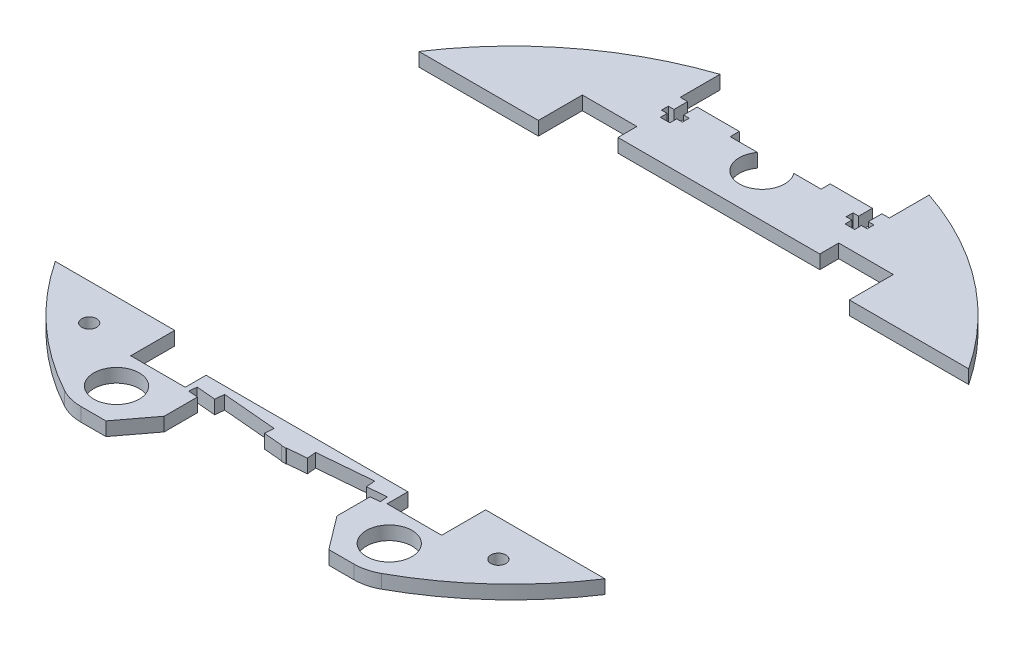
SolidWorks part; units mm, degrees
ref_plane "Front Plane" through (0, 0, 0) normal (0, 0, 1) x (1, 0, 0)
ref_plane "Top Plane" through (0, 0, 0) normal (0, 1, 0) x (1, 0, 0)
ref_plane "Right Plane" through (0, 0, 0) normal (1, 0, 0) x (0, 0, -1)
sketch "Sketch1" plane through (0, 0, 0) normal (0, 1, 0) x (1, 0, 0)
  line L0 (-30.03, -64.8129) -> (30.03, -64.8129)
  line L1 (0, -85) -> (0, 0) construction
  line L2 (0, -85) -> (32.4891, -64.8129) construction
  arc A0 (34.8348, -63.5829) -> (-34.8348, -63.5829) centre (0, 0) ccw
  circle A1 centre (0, -85) radius 38.25 construction
  arc A2 (30.03, -64.8129) -> (34.8348, -63.5829) centre (30.03, -54.8129) ccw
  arc A3 (-30.03, -64.8129) -> (-34.8348, -63.5829) centre (-30.03, -54.8129) cw
  dimension "D1" = 145
  dimension "D2" = 76.5
  dimension "D4" = 10
  dimension "D3" = 85
extrude "Boss-Extrude1" add sketch "Sketch1" along normal blind 3
sketch "Sketch2" plane through (0, 3, 0) normal (0, 1, 0) x (1, 0, 0)
  line L5 (22.2, -49.6757) -> (22.2, -45.1)
  line L6 (22.2, -45.1) -> (-22.2, -45.1)
  line L7 (-22.2, -45.1) -> (-22.2, -49.6757)
  line L8 (22.2, 49.6757) -> (22.2, 45.5)
  line L9 (-34.2, -49.6757) -> (-22.2, -49.6757) construction
  line L10 (-34.2, -49.6757) -> (-34.2, 49.6757) construction
  line L11 (-34.2, 49.6757) -> (-22.2, 49.6757) construction
  line L19 (34.2, 49.6757) -> (22.2, 49.6757) construction
  line L20 (34.2, -49.6757) -> (34.2, 49.6757) construction
  line L21 (34.2, -49.6757) -> (22.2, -49.6757) construction
  line L22 (22.2, 45.5) -> (-22.2, 45.5)
  line L23 (-22.2, 45.5) -> (-22.2, 49.6757)
  line L35 (-34.2, -49.6757) -> (-22.2, -49.6757)
  line L36 (-34.2, -49.6757) -> (-34.2, 49.6757)
  line L37 (-34.2, 49.6757) -> (-22.2, 49.6757)
  line L55 (34.2, 49.6757) -> (22.2, 49.6757)
  line L56 (34.2, -49.6757) -> (34.2, 49.6757)
  line L57 (34.2, -49.6757) -> (22.2, -49.6757)
  dimension "D1" = 45.1
  dimension "D2" = 45.5
extrude "Cut-Extrude1" cut sketch "Sketch2" against normal through all contours L55 L37 L36 L35 L7 L6 L5 L57 L56 region at (0, 3, -0.1256)
sketch "Sketch3" plane through (0, 3, 0) normal (0, 1, 0) x (1, 0, 0)
  line L0 (-34.2, 40) -> (-34.2, -40)
  line L1 (-72.5, -40) -> (-34.2, -40)
  line L2 (-72.5, -40) -> (-72.5, 40)
  line L3 (-72.5, 40) -> (-34.2, 40)
  line L4 (72.5, -40) -> (72.5, 40)
  line L5 (-72.5, -40) -> (72.5, 40) construction
  line L6 (-72.5, 40) -> (72.5, -40) construction
  line L7 (-34.2, -49.6757) -> (-34.2, 49.6757) construction
  line L8 (34.2, 40) -> (34.2, -40)
  line L9 (34.2, -49.6757) -> (34.2, 49.6757) construction
  line L10 (34.2, 40) -> (72.5, 40)
  line L11 (34.2, -40) -> (72.5, -40)
  arc A0 (34.8348, -63.5829) -> (-34.8348, -63.5829) centre (0, 0) ccw construction
  point P0 (0, 0)
  dimension "D1" = 80
extrude "Cut-Extrude2" cut sketch "Sketch3" against normal through all
sketch "Sketch4" plane through (0, 3, 0) normal (0, 1, 0) x (1, 0, 0)
  line L0 (-21.0702, -50.0262) -> (-0.6482, -51.8129)
  line L1 (21.0702, -50.0262) -> (20.922, -48.3326)
  line L2 (0.6482, -51.8129) -> (0.5, -50.1193)
  line L3 (20.922, -48.3326) -> (0.5, -50.1193)
  line L4 (0, 0) -> (0, -64.8129) construction
  line L5 (-30.03, -64.8129) -> (30.03, -64.8129) construction
  line L6 (-20.922, -48.3326) -> (-0.5, -50.1193)
  line L7 (-0.6482, -51.8129) -> (-0.5, -50.1193)
  line L8 (-21.0702, -50.0262) -> (-20.922, -48.3326)
  line L14 (21.0702, -50.0262) -> (0.6482, -51.8129)
  dimension "D1" = 1.7
  dimension "D2" = 20.5
  dimension "D3" = 5
  dimension "D4" = 13
  dimension "D5" = 0.5
extrude "Cut-Extrude3" cut sketch "Sketch4" against normal through all
sketch "Sketch5" plane through (0, 3, 0) normal (0, 1, 0) x (1, 0, 0)
  line L0 (-19, -64.8129) -> (-19, -50.2073)
  line L4 (0.6482, -51.8129) -> (21.0702, -50.0262) construction
  line L5 (16.6882, -48.7031) -> (4.7338, -49.7489)
  line L6 (16.6882, -48.7031) -> (16.5139, -46.7107)
  line L7 (4.7338, -49.7489) -> (4.5595, -47.7565)
  line L8 (16.5139, -46.7107) -> (4.5595, -47.7565)
  line L9 (20.922, -48.3326) -> (0.5, -50.1193) construction
  line L10 (0, 0) -> (0, -50.2073) construction
  line L11 (19, -64.8129) -> (19, -50.2073)
  line L13 (-16.5139, -46.7107) -> (-4.5595, -47.7565)
  line L14 (-4.7338, -49.7489) -> (-4.5595, -47.7565)
  line L15 (-16.6882, -48.7031) -> (-16.5139, -46.7107)
  line L16 (-16.6882, -48.7031) -> (-4.7338, -49.7489)
  line L22 (-30.03, -64.8129) -> (30.03, -64.8129) construction
  line L23 (19, -50.2073) -> (-19, -50.2073)
  line L25 (-19, -64.8129) -> (19, -64.8129)
  point P14 (10.711, -49.226)
  point P15 (10.711, -49.226)
  dimension "D1" = 12
  dimension "D2" = 38
  dimension "D4" = 2
extrude "Cut-Extrude4" cut sketch "Sketch5" against normal through all
sketch "Sketch6" plane through (0, 3, 0) normal (0, 1, 0) x (1, 0, 0)
  line L0 (0, 0) -> (0, 60) construction
  line L1 (-23, 72.5) -> (23, 72.5)
  line L2 (-23, 72.5) -> (-23, 60)
  line L3 (-23, 60) -> (-10, 60)
  line L4 (23, 72.5) -> (23, 60)
  line L5 (10, 60) -> (23, 60)
  line L7 (10, 60) -> (10, 58)
  line L8 (10, 58) -> (-10, 58)
  line L9 (-10, 60) -> (-10, 58)
  arc A1 (60.4669, 40) -> (-60.4669, 40) centre (0, 0) ccw construction
  point P14 (0, 58)
  dimension "D1" = 20
  dimension "D2" = 46
  dimension "D3" = 60
  dimension "D4" = 2
extrude "Cut-Extrude5" cut sketch "Sketch6" against normal through all
sketch "Sketch7" plane through (0, 3, 0) normal (0, 1, 0) x (1, 0, 0)
  line L0 (0, 0) -> (0, -31.2827) construction
  circle A0 centre (-30, -57) radius 5
  circle A4 centre (30, -57) radius 5
  dimension "D1" = 10
  dimension "D2" = 30
  dimension "D3" = 57
extrude "Cut-Extrude6" cut sketch "Sketch7" against normal through all
sketch "Sketch9" plane through (0, 3, 0) normal (0, 1, 0) x (1, 0, 0)
  line L0 (-23, 60) -> (-10, 60) construction
  line L1 (22.62, 57) -> (18.02, 57)
  line L2 (22.62, 57) -> (22.62, 55.5)
  line L3 (22.62, 55.5) -> (18.02, 55.5)
  line L4 (18.02, 57) -> (18.02, 55.5)
  line L5 (0, 0) -> (0, 44) construction
  line L7 (-18.02, 57) -> (-18.02, 55.5)
  line L8 (-22.62, 55.5) -> (-18.02, 55.5)
  line L9 (-22.62, 57) -> (-22.62, 55.5)
  line L10 (-22.62, 57) -> (-18.02, 57)
  point P4 (20.32, 55.5)
  dimension "D1" = 20.32
  dimension "D2" = 1.5
  dimension "D3" = 4.6
  dimension "D4" = 3
extrude "Cut-Extrude8" cut sketch "Sketch9" against normal through all
sketch "Sketch10" plane through (0, 3, 0) normal (0, 1, 0) x (1, 0, 0)
  line L0 (22.62, 57) -> (18.02, 57) construction
  line L1 (21.37, 57) -> (19.27, 57)
  line L2 (21.37, 57) -> (21.37, 60)
  line L3 (21.37, 60) -> (19.27, 60)
  line L4 (19.27, 57) -> (19.27, 60)
  line L5 (-23, 60) -> (-10, 60) construction
  line L6 (0, 0) -> (0, 44) construction
  line L8 (18.02, 55.5) -> (22.62, 55.5) construction
  line L9 (21.37, 55.5) -> (19.27, 55.5)
  line L10 (21.37, 55.5) -> (21.37, 54)
  line L11 (21.37, 54) -> (19.27, 54)
  line L12 (19.27, 55.5) -> (19.27, 54)
  line L13 (-19.27, 55.5) -> (-19.27, 54)
  line L14 (-21.37, 54) -> (-19.27, 54)
  line L15 (-21.37, 55.5) -> (-21.37, 54)
  line L16 (-21.37, 55.5) -> (-19.27, 55.5)
  line L17 (-19.27, 57) -> (-19.27, 60)
  line L18 (-21.37, 60) -> (-19.27, 60)
  line L19 (-21.37, 57) -> (-21.37, 60)
  line L20 (-21.37, 57) -> (-19.27, 57)
  point P14 (20.32, 57)
  point P16 (20.32, 57)
  dimension "D1" = 2.1
  dimension "D2" = 6
extrude "Cut-Extrude9" cut sketch "Sketch10" against normal through all
sketch "Sketch11" plane through (0, 3, 0) normal (0, 1, 0) x (1, 0, 0)
  line L0 (0, 0) -> (0, 55) construction
  circle A0 centre (0, 55) radius 5
  dimension "D2" = 10
  dimension "D1" = 55
extrude "Cut-Extrude10" cut sketch "Sketch11" against normal through all
sketch "Sketch13" plane through (0, 3, 0) normal (0, 1, 0) x (1, 0, 0)
  line L0 (19, -57.5101) -> (24.515, -64.8129)
  line L1 (19, -64.8129) -> (19, -50.2073) construction
  line L2 (19, -64.8129) -> (30.03, -64.8129) construction
  line L3 (24.515, -64.8129) -> (19, -64.8129)
  line L4 (19, -64.8129) -> (19, -57.5101)
  line L5 (0, 0) -> (0, -25.0729) construction
  line L6 (-19, -64.8129) -> (-19, -57.5101)
  line L7 (-24.515, -64.8129) -> (-19, -64.8129)
  line L8 (-19, -57.5101) -> (-24.515, -64.8129)
extrude "Cut-Extrude11" cut sketch "Sketch13" against normal through all
sketch "Sketch14" plane through (0, 3, 0) normal (0, 1, 0) x (1, 0, 0)
  line L1 (0, 0) -> (0, -20.685) construction
  circle A0 centre (45, -48) radius 1.65
  circle A1 centre (-45, -48) radius 1.65
  dimension "D3" = 3.3
  dimension "D1" = 45
  dimension "D2" = 48
extrude "Cut-Extrude12" cut sketch "Sketch14" against normal through all
equation "\"smallPulleyTeeth\"= 30"
equation "\"largePulleyTeeth\"= 30"
equation "\"eighthThick\"= 3.0mm"
equation "\"sixteenthThick\" = 1.7mm"
equation "\"quarterThick\"=6.0mm"
equation "\"OD\" = 145mm"
equation "\"puckAngle\" = 60.5deg"
equation "\"puckDiam\" = 76.5mm"
equation "\"axlePress\" = 5.9mm"
equation "\"press\" = 0.2mm"
equation "\"wheelClear\" = 0.3mm"
equation "\"10-32clear\" = 4.8mm"
equation "\"6-32clear\" = 3.3mm"
equation "\"8-32clear\" = 4.0mm"
equation "\"4-40clear\" = 3.0mm"
equation "\"wheelHeight\" = 22mm"
equation "\"wheelWell\" = 65mm"
equation "\"D1@Sketch1\"=\"OD\""
equation "\"D1@Boss-Extrude1\"=\"eighthThick\""
equation "\"D2@Sketch1\"=\"puckDiam\""
equation "\"puckDist\" = 85mm"
equation "\"scoopFillet\" = 5mm"
equation "\"10-32tap\" = 4.45mm"
equation "\"ledSmall\" = 3.1mm"
equation "\"ledLarge\" = 4.2mm"
equation "\"ledLength\" = 4.2mm"
equation "\"D3@Sketch1\"=\"puckDist\""
